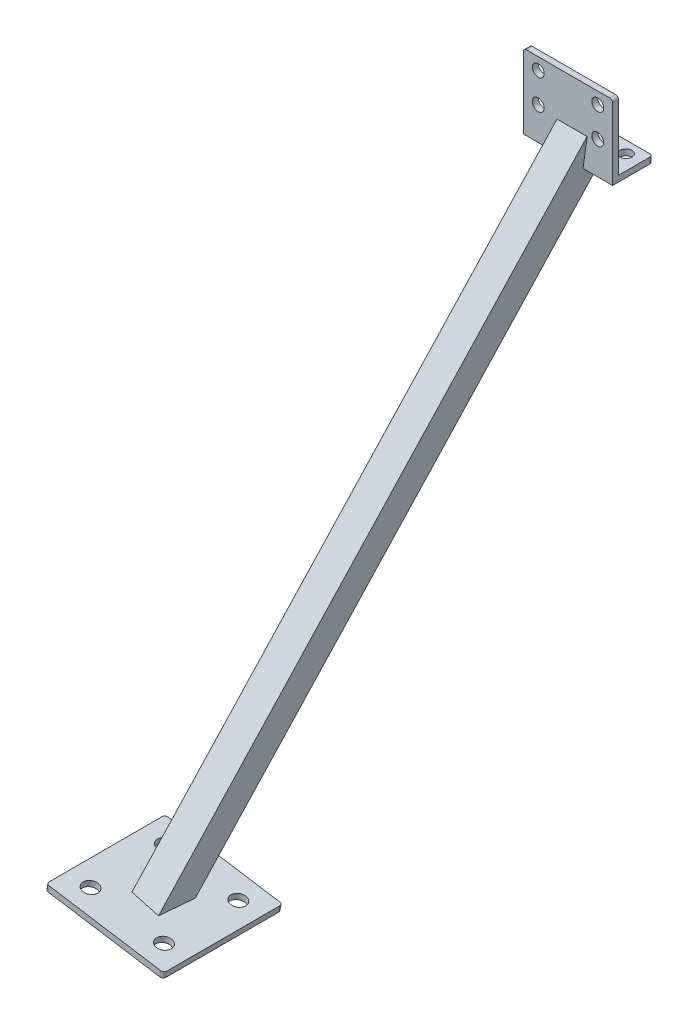
SolidWorks part; units mm, degrees
ref_plane "Front Plane" through (0, 0, 0) normal (0, 0, 1) x (1, 0, 0)
ref_plane "Top Plane" through (0, 0, 0) normal (0, 1, 0) x (1, 0, 0)
ref_plane "Right Plane" through (0, 0, 0) normal (1, 0, 0) x (0, 0, -1)
sketch "Sketch1" plane through (0, 0, 0) normal (1, 0, 0) x (0, 0, -1)
  line L0 (0, 0) -> (0, 50)
  line L1 (0, 50) -> (4, 50)
  line L2 (4, 50) -> (4, 4)
  line L3 (4, 4) -> (27, 4)
  line L4 (27, 4) -> (27, 0)
  line L5 (27, 0) -> (0, 0)
  dimension "D1" = 4
  dimension "D2" = 4
  dimension "D3" = 50
  dimension "D4" = 27
extrude "Boss-Extrude1" add sketch "Sketch1" along normal blind 60
ref_plane "Plane1" through (0, 0, 0) normal (0, -0.866, 0.5) x (-1, 0, 0)
sketch "Sketch2" plane through (0, 0, 0) normal (0, -0.866, 0.5) x (-1, 0, 0)
  line L0 (-30, 0) -> (-30, 23.3827)
  line L1 (-60, 0) -> (0, 0) construction
  line L2 (-60, 23.3827) -> (0, 23.3827) construction
ref_plane "Plane2" through (0.7342, 4.0142, -2.3176) normal (-0.1564, -0.8554, 0.4938) x (0, -0.5, -0.866)
sketch "Sketch3" plane through (0.7342, 4.0142, -2.3176) normal (-0.1564, -0.8554, 0.4938) x (0, -0.5, -0.866)
  line L0 (-9, 38.6307) -> (9, 38.6307)
  line L1 (-10, 39.6307) -> (10, 39.6307)
  line L2 (-10, 39.6307) -> (-10, 19.6307)
  line L3 (-10, 19.6307) -> (10, 19.6307)
  line L4 (10, 39.6307) -> (10, 19.6307)
  line L5 (-10, 39.6307) -> (10, 19.6307) construction
  line L6 (-10, 19.6307) -> (10, 39.6307) construction
  line L7 (9, 38.6307) -> (9, 20.6307)
  line L8 (-9, 20.6307) -> (9, 20.6307)
  line L9 (-9, 38.6307) -> (-9, 20.6307)
  point P0 (0, 29.6307)
  dimension "D1" = 20
  dimension "D2" = 20
  dimension "D3" = 1
extrude "Boss-Extrude2" add sketch "Sketch3" along normal blind 500 and the other way blind 20
sketch "Sketch4" plane through (0, 0, 0) normal (-1, 0, 0) x (0, 0, 1)
  line L0 (-4, 4) -> (-4, 34.4259)
  line L1 (-4, 4) -> (-4, 50) construction
  line L2 (-4, 34.4259) -> (-31.384, 4)
  line L3 (-27, 4) -> (-4, 4) construction
  line L4 (-31.384, 4) -> (-4, 4)
extrude "Cut-Extrude1" cut sketch "Sketch4" against normal blind 60
ref_plane "Plane3" through (-56.757, -358.3495, 0) normal (0.1564, 0.9877, 0) x (0.9877, -0.1564, 0)
sketch "Sketch6" plane through (-56.757, -358.3495, 0) normal (0.1564, 0.9877, 0) x (0.9877, -0.1564, 0)
  line L0 (28.4656, -256.3645) -> (8.5312, -254.8002) construction
  line L2 (19.2115, 0) -> (8.5312, -254.8002) construction
  line L4 (60.6025, -165.5937) -> (-19.3975, -165.5937)
  line L5 (60.6025, -165.5937) -> (60.6025, -245.5937)
  line L6 (60.6025, -245.5937) -> (-19.3975, -245.5937)
  line L7 (-19.3975, -165.5937) -> (-19.3975, -245.5937)
  line L8 (60.6025, -165.5937) -> (-19.3975, -245.5937) construction
  line L9 (60.6025, -245.5937) -> (-19.3975, -165.5937) construction
  point P0 (20.6025, -205.5937)
  point P6 (20.6025, -205.5937)
  dimension "D1" = 50
  dimension "D2" = 10
  dimension "D3" = 80
  dimension "D4" = 80
extrude "Boss-Extrude3" add sketch "Sketch6" along normal blind 4
sketch "Sketch7" plane through (-56.757, -358.3495, 0) normal (-0.1564, -0.9877, 0) x (0.9877, -0.1564, 0)
  line L1 (-14.2325, 168.7738) -> (52.3005, 168.7738)
  line L2 (-14.2325, 168.7738) -> (-14.2325, 268.7738)
  line L3 (-14.2325, 268.7738) -> (52.3005, 268.7738)
  line L4 (52.3005, 168.7738) -> (52.3005, 268.7738)
  line L5 (-14.2325, 168.7738) -> (52.3005, 268.7738) construction
  line L6 (-14.2325, 268.7738) -> (52.3005, 168.7738) construction
  point P0 (19.034, 218.7738)
  dimension "D1" = 100
extrude "Cut-Extrude2" cut sketch "Sketch7" along normal blind 100
sketch "Sketch8" plane through (0, 0, 0) normal (0, 0, 1) x (1, 0, 0)
  circle A0 centre (10, 22) radius 4 construction
  circle A1 centre (50, 22) radius 4 construction
  circle A2 centre (50, 42) radius 4 construction
  circle A3 centre (10, 42) radius 4 construction
  circle A4 centre (10, 22) radius 4
  circle A5 centre (50, 22) radius 4
  circle A6 centre (50, 42) radius 4
  circle A7 centre (10, 42) radius 4
extrude "Cut-Extrude3" cut sketch "Sketch8" against normal up to next
sketch "Sketch9" plane through (0, 0, 0) normal (0, -1, 0) x (1, 0, 0)
  circle A0 centre (50, -19) radius 4 construction
  circle A1 centre (10, -19) radius 4 construction
  circle A2 centre (50, -19) radius 4
  circle A3 centre (10, -19) radius 4
extrude "Cut-Extrude4" cut sketch "Sketch9" against normal up to next
sketch "Sketch10" plane through (-56.757, -358.3495, 0) normal (-0.1564, -0.9877, 0) x (0.9877, -0.1564, 0)
  line L0 (-19.3975, 245.5937) -> (60.6025, 245.5937) construction
  line L1 (-19.3975, 165.5937) -> (-19.3975, 245.5937) construction
  circle A0 centre (-4.3975, 230.5937) radius 5
  circle A1 centre (45.6025, 230.5937) radius 5
  circle A2 centre (45.6025, 180.5937) radius 5
  circle A3 centre (-4.3975, 180.5937) radius 5
  dimension "D1" = 10
  dimension "D2" = 15
  dimension "D3" = 15
  dimension "D4" = 2
  dimension "D5" = 2
extrude "Cut-Extrude5" cut sketch "Sketch10" against normal up to next
fillet "Fillet1" radius 2 4 edges at (-75.6028, -353.3397, 245.5937) (-75.6028, -353.3397, 165.5937) (3.4123, -365.8545, 165.5937) (3.4123, -365.8545, 245.5937)
fillet "Fillet2" radius 2 4 edges at (60, 2, -27) (0, 2, -27) (60, 50, -2) (0, 50, -2)
